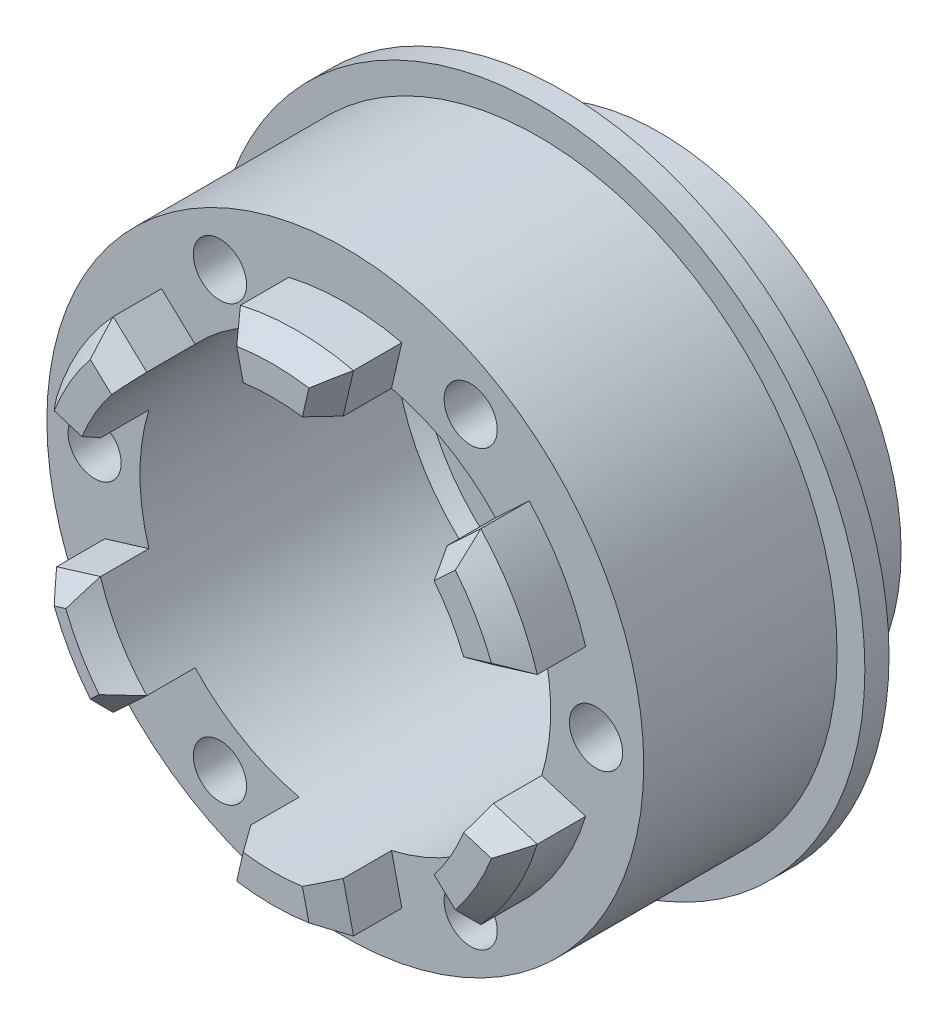
SolidWorks part; units mm, degrees
ref_plane "정면" through (0, 0, 0) normal (0, 0, 1) x (1, 0, 0)
ref_plane "윗면" through (0, 0, 0) normal (0, 1, 0) x (1, 0, 0)
ref_plane "우측면" through (0, 0, 0) normal (1, 0, 0) x (0, 0, -1)
sketch "스케치1" plane through (0, 0, 0) normal (0, 0, 1) x (1, 0, 0)
  circle A0 centre (0, 0) radius 10
  dimension "D1" = 20
extrude "보스-돌출1" add sketch "스케치1" along normal blind 2
sketch "스케치2" plane through (0, 0, 2) normal (0, 0, 1) x (1, 0, 0)
  circle A0 centre (0, 0) radius 10
  circle A1 centre (0, 0) radius 8.5
  circle A5 centre (0, 0) radius 10 construction
  dimension "D1" = 1.5
extrude "보스-돌출2" add sketch "스케치2" along normal blind 2
sketch "스케치4" plane through (0, 0, 4) normal (0, 0, 1) x (1, 0, 0)
  circle A0 centre (0, 0) radius 13.5
  circle A1 centre (0, 0) radius 8.5
  circle A2 centre (0, 0) radius 8.5 construction
  dimension "D1" = 27
extrude "보스-돌출3" add sketch "스케치4" along normal blind 1
sketch "스케치5" plane through (0, 0, 5) normal (0, 0, 1) x (1, 0, 0)
  circle A0 centre (0, 0) radius 8.5
  circle A1 centre (0, 0) radius 12.35
  circle A2 centre (0, 0) radius 8.5 construction
  dimension "D1" = 24.7
extrude "보스-돌출4" add sketch "스케치5" along normal blind 8
sketch "스케치6" plane through (0, 0, 13) normal (0, 0, 1) x (1, 0, 0)
  circle A0 centre (0, 0) radius 10.375 construction
  circle A6 centre (0, 0) radius 8.5 construction
  circle A8 centre (10.375, 0) radius 1.1
  circle A9 centre (5.1875, -8.985) radius 1.1
  circle A10 centre (-5.1875, -8.985) radius 1.1
  circle A11 centre (-10.375, 0) radius 1.1
  circle A12 centre (-5.1875, 8.985) radius 1.1
  circle A13 centre (5.1875, 8.985) radius 1.1
  point P19 (0, 0)
  point P20 (0, 0)
  dimension "D1" = 1.875
  dimension "D2" = 2.2
  dimension "D3" = 6
extrude "컷-돌출1" cut sketch "스케치6" against normal blind 8
sketch "스케치7" plane through (0, 0, 0) normal (0, 0, -1) x (-1, 0, 0)
  circle A0 centre (0, 0) radius 7 construction
  circle A5 centre (0, 0) radius 3
  circle A6 centre (-7, 0) radius 1.15
  circle A7 centre (7, 0) radius 1.15
  circle A9 centre (0, 7) radius 1.15
  circle A11 centre (0, -7) radius 1.15
  dimension "D1" = 14
  dimension "D2" = 2.3
  dimension "D4" = 6
extrude "컷-돌출2" cut sketch "스케치7" against normal through all
sketch "스케치10" plane through (0, 0, 13) normal (0, 0, 1) x (1, 0, 0)
  line L24 (2.3395, 10.1334) -> (1.9121, 8.2821)
  line L25 (-2.3395, 10.1334) -> (-1.9121, 8.2821)
  line L26 (7.6061, 7.0928) -> (6.2165, 5.797)
  line L27 (9.9456, 3.0407) -> (8.1286, 2.4852)
  line L28 (9.9456, -3.0407) -> (8.1286, -2.4852)
  line L29 (7.6061, -7.0928) -> (6.2165, -5.797)
  line L30 (2.3395, -10.1334) -> (1.9121, -8.2821)
  line L31 (-2.3395, -10.1334) -> (-1.9121, -8.2821)
  line L32 (-7.6061, -7.0928) -> (-6.2165, -5.797)
  line L33 (-9.9456, -3.0407) -> (-8.1286, -2.4852)
  line L34 (-9.9456, 3.0407) -> (-8.1286, 2.4852)
  line L35 (-7.6061, 7.0928) -> (-6.2165, 5.797)
  arc A0 (-7.6061, 7.0928) -> (-9.9456, 3.0407) centre (0, 0) ccw
  arc A1 (-8.1286, -2.4852) -> (-6.2165, -5.797) centre (0, 0) ccw
  arc A2 (2.3395, 10.1334) -> (-2.3395, 10.1334) centre (0, 0) ccw
  arc A3 (9.9456, 3.0407) -> (7.6061, 7.0928) centre (0, 0) ccw
  arc A4 (7.6061, -7.0928) -> (9.9456, -3.0407) centre (0, 0) ccw
  arc A5 (-2.3395, -10.1334) -> (2.3395, -10.1334) centre (0, 0) ccw
  arc A6 (-9.9456, -3.0407) -> (-7.6061, -7.0928) centre (0, 0) ccw
  arc A7 (-1.9121, -8.2821) -> (1.9121, -8.2821) centre (0, 0) ccw
  arc A8 (6.2165, -5.797) -> (8.1286, -2.4852) centre (0, 0) ccw
  arc A9 (8.1286, 2.4852) -> (6.2165, 5.797) centre (0, 0) ccw
  arc A10 (1.9121, 8.2821) -> (-1.9121, 8.2821) centre (0, 0) ccw
  arc A11 (-6.2165, 5.797) -> (-8.1286, 2.4852) centre (0, 0) ccw
  circle A12 centre (0, 0) radius 8.5 construction
  circle A13 centre (0, 0) radius 8.5 construction
  point P9 (0, 0)
  point P10 (0, 0)
  point P21 (0, 0)
  point P30 (0, 0)
  point P48 (0, 0)
  point P61 (0, 0)
  dimension "D1" = 1.9
  dimension "D4" = 6
extrude "보스-돌출5" add sketch "스케치10" along normal blind 3
chamfer "모따기1" distance 1 angle 35 19 edges at (-9.0067, -5.2, 16) (0, -10.4, 16) (9.0067, -5.2, 16) (9.0067, 5.2, 16) (0, 10.4, 16) (-9.0067, 5.2, 16) (-9.0371, -2.7629, 16) (-7.3612, -4.25, 16) (-6.9113, -6.4449, 16) (2.1258, -9.2078, 16) (-2.1258, -9.2078, 16) (6.9113, -6.4449, 16) (9.0371, -2.7629, 16) (9.0371, 2.7629, 16) (6.9113, 6.4449, 16) (2.1258, 9.2078, 16) (-2.1258, 9.2078, 16) (-9.0371, 2.7629, 16) (-6.9113, 6.4449, 16) first distance on face at (-8.8912, -5.1334, 14.5) first distance on face at (0, -10.2667, 14.5) first distance on face at (8.8912, -5.1334, 14.5) first distance on face at (8.8912, 5.1334, 14.5) first distance on face at (0, 10.2667, 14.5) first distance on face at (-8.8912, 5.1334, 14.5) first distance on face at (-9.0371, -2.7629, 14.5) first distance on face at (8.5, 0, 2) first distance on face at (-6.9113, -6.4449, 14.5) first distance on face at (2.1258, -9.2078, 14.5) first distance on face at (-2.1258, -9.2078, 14.5) first distance on face at (6.9113, -6.4449, 14.5) first distance on face at (9.0371, -2.7629, 14.5) first distance on face at (9.0371, 2.7629, 14.5) first distance on face at (6.9113, 6.4449, 14.5) first distance on face at (2.1258, 9.2078, 14.5) first distance on face at (-2.1258, 9.2078, 14.5) first distance on face at (-9.0371, 2.7629, 14.5) first distance on face at (-6.9113, 6.4449, 14.5)
chamfer "모따기2" distance 0.5 angle 45 1 edges at (8.5, 0, 2)
